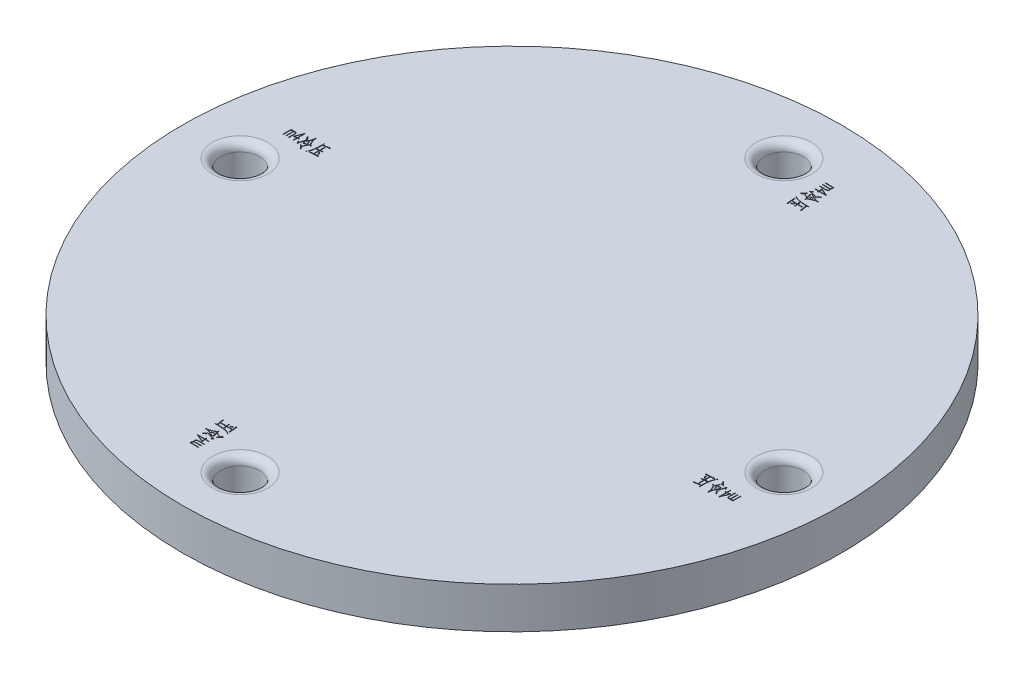
SolidWorks part; units mm, degrees
ref_plane "前视基准面" through (0, 0, 0) normal (0, 0, 1) x (1, 0, 0)
ref_plane "上视基准面" through (0, 0, 0) normal (0, 1, 0) x (1, 0, 0)
ref_plane "右视基准面" through (0, 0, 0) normal (1, 0, 0) x (0, 0, -1)
sketch "草图1" plane through (0, 0, 0) normal (0, 1, 0) x (1, 0, 0)
  line L14 (0, 0) -> (35, 0)
  line L15 (0, 0) -> (0, -35)
  circle A0 centre (0, 0) radius 40
  circle A5 centre (0, 0) radius 35
  circle A6 centre (0, 0) radius 34
  circle A7 centre (0, -34) radius 1
  circle A8 centre (0, -33) radius 2
  dimension "D1" = 80
  dimension "D2" = 70
  dimension "D3" = 68
sketch "草图3" plane through (0, 0, 0) normal (0, 1, 0) x (1, 0, 0)
  circle A0 centre (0, -33) radius 2 construction
  circle A1 centre (0, -33) radius 2
  circle A2 centre (0, 0) radius 33
  circle A3 centre (-32.999, 0.001) radius 2
  circle A4 centre (0.002, 33) radius 2
  circle A5 centre (33.001, -0.001) radius 2
  point P6 (0, 0)
  point P15 (0.001, 0)
  dimension "D2" = 4
  dimension "D1" = 4
sketch "草图4" plane through (0, 0, 0) normal (0, 1, 0) x (1, 0, 0)
  circle A0 centre (0, 0) radius 40 construction
  circle A1 centre (0, 0) radius 40
extrude "凸台-拉伸1" add sketch "草图4" along normal blind 5
sketch "草图6" plane through (0, 0, 0) normal (0, 1, 0) x (1, 0, 0)
  circle A14 centre (0.002, 33) radius 2 construction
  circle A16 centre (-32.999, 0.001) radius 2.35
  circle A17 centre (0, -33) radius 2.35
  circle A18 centre (33.001, -0.001) radius 2.35
  circle A19 centre (0.002, 33) radius 2.35
  dimension "D2" = 4.7
extrude "固定轴承内圈的四个冷压孔" cut sketch "草图6" along normal up to surface (5 mm away) up to face at (0, 5, 40)
fillet "圆角1" radius 1 4 edges at (0.002, 5, -30.65) (33.001, 5, 2.351) (0, 5, 35.35) (-32.999, 5, 2.349)
ref_plane "基准面1" through (0, 5, 0) normal (0, 1, 0) x (1, 0, 0)
sketch "草图8" plane through (0, 5, 0) normal (0, 1, 0) x (1, 0, 0)
  line L0 (0.002, 33) -> (-32.999, 0.001)
  line L1 (0.002, 33) -> (33.001, -0.001)
  line L2 (-32.999, 0.001) -> (0, -33)
  line L3 (33.001, -0.001) -> (0, -33)
  line L5 (33.001, -0.001) -> (28.0007, -0.001)
  line L6 (33.001, -0.001) -> (33.001, -5.001)
  line L7 (33.001, -5.001) -> (28.0007, -5.001)
  line L8 (28.0007, -0.001) -> (28.0007, -5.001)
  line L9 (0.002, 33) -> (5.002, 33)
  line L10 (0.002, 33) -> (0.002, 27.9997)
  line L11 (0.002, 27.9997) -> (5.002, 27.9997)
  line L12 (5.002, 33) -> (5.002, 27.9997)
  line L13 (-32.999, 0.001) -> (-27.9987, 0.001)
  line L14 (-32.999, 0.001) -> (-32.999, 5.001)
  line L15 (-32.999, 5.001) -> (-27.9987, 5.001)
  line L16 (-27.9987, 0.001) -> (-27.9987, 5.001)
  line L17 (0, -33) -> (-5, -33)
  line L18 (0, -33) -> (0, -27.9997)
  line L19 (0, -27.9997) -> (-5, -27.9997)
  line L20 (-5, -33) -> (-5, -27.9997)
  circle A0 centre (0, 0) radius 33
  circle A1 centre (-32.999, 0.001) radius 2.35 construction
  circle A2 centre (-32.999, 0.001) radius 2.35
  circle A3 centre (0.002, 33) radius 2.35 construction
  circle A4 centre (0.002, 33) radius 2.35
  circle A5 centre (0, -33) radius 2.35 construction
  circle A6 centre (0, -33) radius 2.35
  circle A7 centre (0, 0) radius 40 construction
  circle A8 centre (0, 0) radius 40
  dimension "D1" = 5
  dimension "D5" = 66
  dimension "D6" = 80
  dimension "D2" = 5
  dimension "D3" = 5
  dimension "D4" = 5
sketch "草图9" plane through (0, 5, 0) normal (0, 1, 0) x (1, 0, 0)
  text T0 "m4冷压" font "汉仪长仿宋体" height 1.5
  text T1 "m4冷压" font "汉仪长仿宋体" height 1.5
  text T2 "m4冷压" font "汉仪长仿宋体" height 1.5
  text T3 "m4冷压\r\n" font "汉仪长仿宋体" height 1.5
extrude "切除-拉伸1" cut sketch "草图9" against normal blind 0.5
